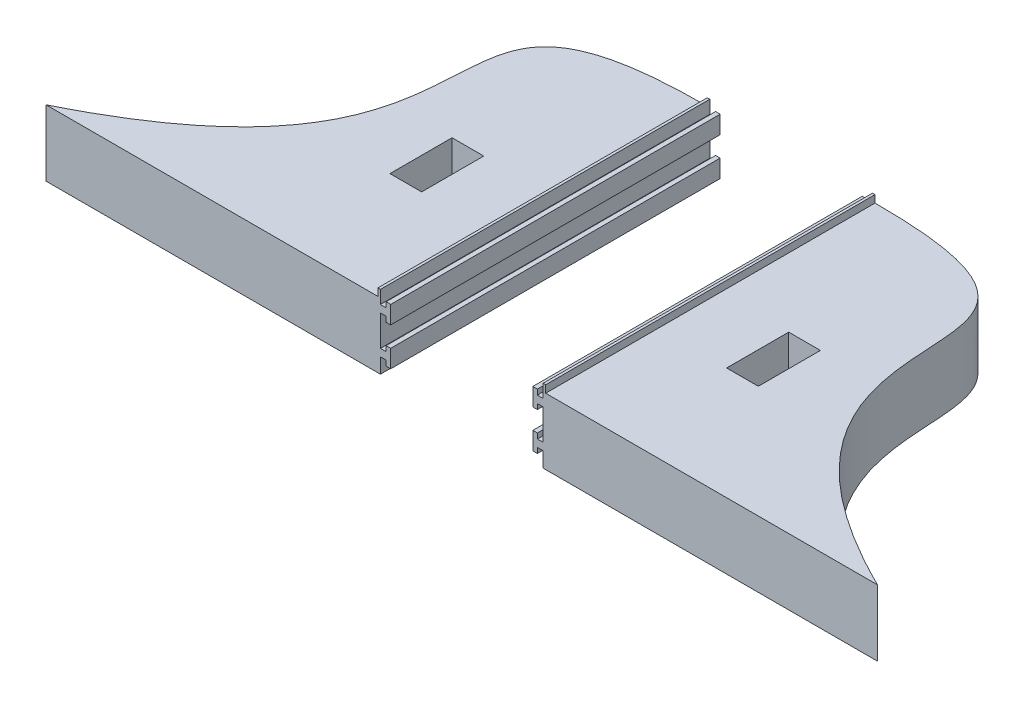
SolidWorks part; units mm, degrees
material "PLA"
ref_plane "Front Plane" through (0, 0, 0) normal (0, 0, 1) x (1, 0, 0)
ref_plane "Top Plane" through (0, 0, 0) normal (0, 1, 0) x (1, 0, 0)
ref_plane "Right Plane" through (0, 0, 0) normal (1, 0, 0) x (0, 0, -1)
ref_plane "Rail start" through (0, 0, -130) normal (0, 0, 1) x (1, 0, 0)
sketch "Sketch1" plane through (0, 0, -130) normal (0, 0, 1) x (1, 0, 0)
  line L440 (-32.1, -15.0497) -> (-32.1, -21)
  line L441 (-29.8428, -15.0497) -> (-32.1, -15.0497)
  line L442 (-29.8428, -17.1189) -> (-29.8428, -15.0497)
  line L443 (-28.0428, -17.1189) -> (-29.8428, -17.1189)
  line L444 (-28.0428, -10.1) -> (-28.0428, -17.1189)
  line L445 (-29.8428, -10.1) -> (-28.0428, -10.1)
  line L446 (-29.8428, -12.1692) -> (-29.8428, -10.1)
  line L447 (-32.1, -12.1692) -> (-29.8428, -12.1692)
  line L448 (-32.1, -0.0497) -> (-32.1, -12.1692)
  line L449 (-29.8428, -0.0497) -> (-32.1, -0.0497)
  line L450 (-29.8428, -2.1189) -> (-29.8428, -0.0497)
  line L451 (-28.0428, -2.1189) -> (-29.8428, -2.1189)
  line L452 (-28.0428, 4.9) -> (-28.0428, -2.1189)
  line L453 (-29.8428, 4.9) -> (-28.0428, 4.9)
  line L454 (-29.8428, 2.8308) -> (-29.8428, 4.9)
  line L455 (-32.1, 2.8308) -> (-29.8428, 2.8308)
  line L456 (-32.1, 8) -> (-32.1, 2.8308)
  line L457 (-32.1, -15.0497) -> (-32.1, -21)
  line L458 (-29.8428, -15.0497) -> (-32.1, -15.0497)
  line L459 (-29.8428, -17.1189) -> (-29.8428, -15.0497)
  line L460 (-28.0428, -17.1189) -> (-29.8428, -17.1189)
  line L461 (-28.0428, -10.1) -> (-28.0428, -17.1189)
  line L462 (-29.8428, -10.1) -> (-28.0428, -10.1)
  line L463 (-29.8428, -12.1692) -> (-29.8428, -10.1)
  line L464 (-32.1, -12.1692) -> (-29.8428, -12.1692)
  line L465 (-32.1, -0.0497) -> (-32.1, -12.1692)
  line L466 (-29.8428, -0.0497) -> (-32.1, -0.0497)
  line L467 (-29.8428, -2.1189) -> (-29.8428, -0.0497)
  line L468 (-28.0428, -2.1189) -> (-29.8428, -2.1189)
  line L469 (-28.0428, 4.9) -> (-28.0428, -2.1189)
  line L470 (-29.8428, 4.9) -> (-28.0428, 4.9)
  line L471 (-29.8428, 2.8308) -> (-29.8428, 4.9)
  line L472 (-32.1, 2.8308) -> (-29.8428, 2.8308)
  line L473 (-32.1, 8) -> (-32.1, 2.8308)
  line L474 (-32.1, -21) -> (-33.1, -21)
  line L475 (-33.1, -21) -> (-33.1, 8)
  line L476 (-33.1, 8) -> (-32.1, 8)
  dimension "D1" = 0.1
extrude "Boss-Extrude1" add sketch "Sketch1" along normal up to surface (130 mm away)
sketch "Sketch2" plane through (75.2969, -0.8945, -218.7008) normal (0, 1, 0) x (1, 0, 0)
  line L0 (-108.3969, -88.7008) -> (-108.3969, -218.7008)
  line L2 (-239.3767, -218.7008) -> (-108.3969, -218.7008)
  line L4 (-108.3969, -218.7008) -> (-108.3969, -88.7008) construction
  line L5 (-107.3969, -218.7008) -> (-107.3969, -88.7008) construction
  line L9 (-108.3969, -88.7008) -> (-226.6247, -88.7008) construction
  line L10 (-226.6247, -88.7008) -> (-107.3969, -153.7008) construction
  line L11 (-107.3969, -153.7008) -> (-239.3767, -218.7008) construction
  line L15 (-108.3969, -218.7008) -> (-108.3969, -88.7008) construction
  spline S0 degree 3 poles (-108.3969, -88.7008) (-226.6247, -88.7008) (-107.3969, -153.7008) (-239.3767, -218.7008) knots 0 0 0 0 1 1 1 1
extrude "Boss-Extrude2" add sketch "Sketch2" along normal blind 6 and the other way up to surface (20.1055 mm away) other way up to face at (-32.6, -21, -65)
sketch "Sketch3" plane through (0, 5.1055, 0) normal (0, 1, 0) x (1, 0, 0)
  line L0 (-72.6859, 44.3374) -> (-60.1779, 44.3374)
  line L1 (-72.4319, 68.5914) -> (-60.4319, 68.5914) construction
  line L2 (-72.4319, 68.5914) -> (-72.4319, 44.5914) construction
  line L3 (-72.4319, 44.5914) -> (-60.4319, 44.5914) construction
  line L4 (-60.4319, 68.5914) -> (-60.4319, 44.5914) construction
  line L5 (-66.4319, 44.5914) -> (-66.4319, 68.5914) construction
  line L6 (-72.4319, 56.5914) -> (-60.4319, 56.5914) construction
  line L7 (0, 56.5914) -> (-60.4319, 56.5914) construction
  line L8 (-60.1779, 68.8454) -> (-60.1779, 44.3374)
  line L9 (-72.6859, 68.8454) -> (-60.1779, 68.8454)
  line L10 (-72.6859, 68.8454) -> (-72.6859, 44.3374)
  point P0 (-66.4319, 56.5914)
  point P4 (0, 0)
  point P5 (0, 65.7929)
  point P7 (0, 56.5914)
  dimension "D1" = 24
  dimension "D2" = 12
  dimension "D3" = 0.254
extrude "Cut-Extrude1" cut sketch "Sketch3" against normal blind 20
mirror "Mirror1" about plane through (0, 0, 0) normal (1, 0, 0) of bodies 104 102
